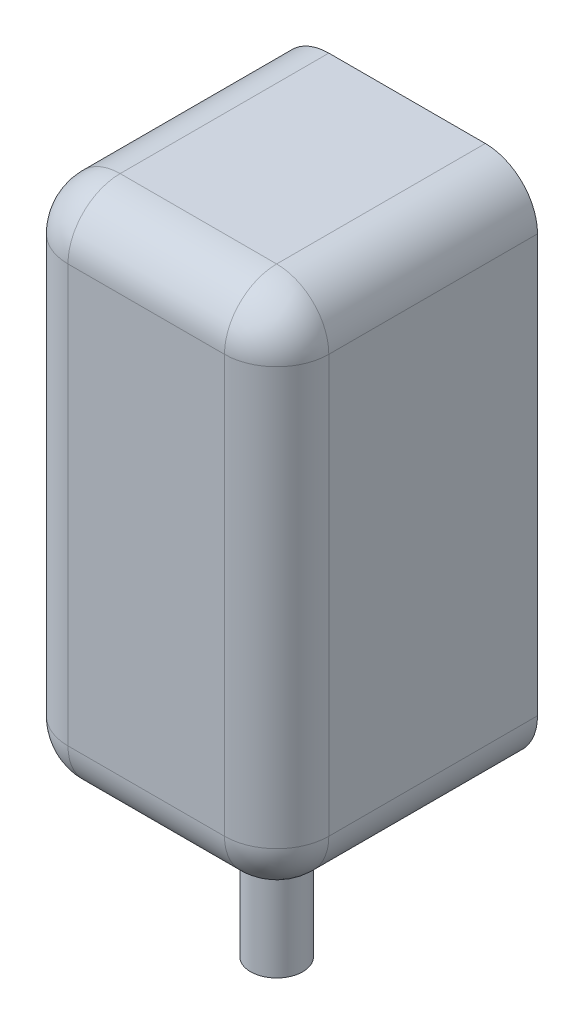
SolidWorks part; units mm, degrees
ref_plane "Front Plane" through (0, 0, 0) normal (0, 0, 1) x (1, 0, 0)
ref_plane "Top Plane" through (0, 0, 0) normal (0, 1, 0) x (1, 0, 0)
ref_plane "Right Plane" through (0, 0, 0) normal (1, 0, 0) x (0, 0, -1)
sketch "Sketch1" plane through (0, 0, 0) normal (0, 1, 0) x (1, 0, 0)
  line L1 (-25, 25) -> (25, 25)
  line L2 (-25, 25) -> (-25, -25)
  line L3 (-25, -25) -> (25, -25)
  line L4 (25, 25) -> (25, -25)
  line L5 (-25, 25) -> (25, -25) construction
  line L6 (-25, -25) -> (25, 25) construction
  point P1 (0, 0)
  dimension "D1" = 50
  dimension "D2" = 50
extrude "Boss-Extrude1" add sketch "Sketch1" along normal blind 100
sketch "Sketch2" plane through (0, 0, 0) normal (0, -1, 0) x (1, 0, 0)
  circle A0 centre (0, 0) radius 5
  dimension "D1" = 10
extrude "Boss-Extrude2" add sketch "Sketch2" along normal blind 30
fillet "Fillet1" radius 10 4 edges at (0, 0, 25) (0, 100, 25) (25, 50, 25) (-25, 50, 25)
fillet "Fillet2" radius 10 8 edges at (-22.0711, 97.0711, 22.0711) (22.0711, 97.0711, 22.0711) (-22.0711, 2.9289, 22.0711) (22.0711, 2.9289, 22.0711) (-25, 100, -5) (25, 100, -5) (-25, 0, -5) (25, 0, -5)
